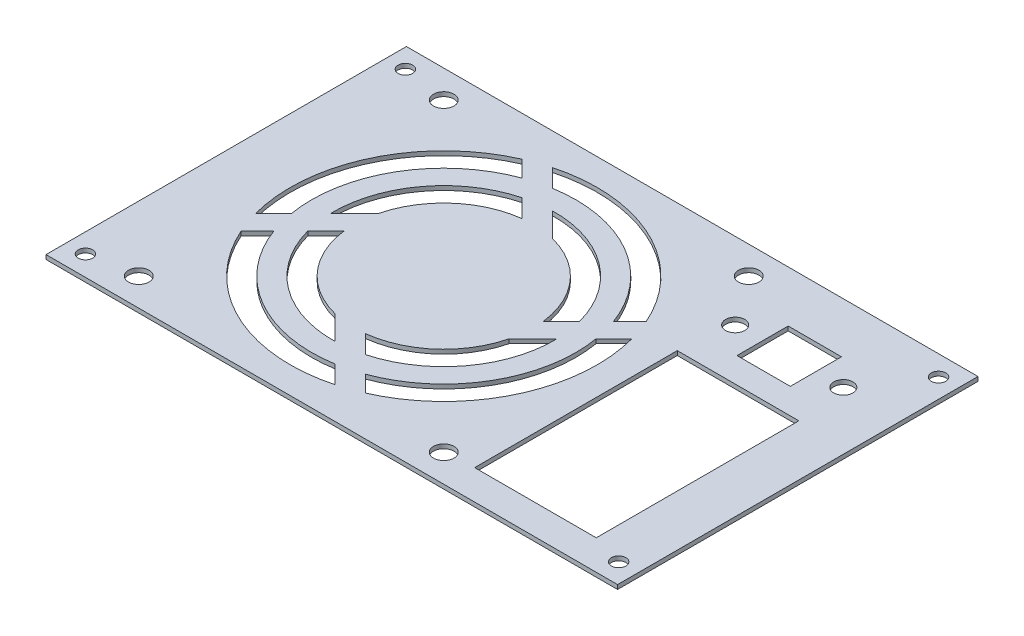
SolidWorks part; units mm, degrees
material "Thornel Mat VMA"
ref_plane "Front Plane" through (0, 0, 0) normal (0, 0, 1) x (1, 0, 0)
ref_plane "Top Plane" through (0, 0, 0) normal (0, 1, 0) x (1, 0, 0)
ref_plane "Right Plane" through (0, 0, 0) normal (1, 0, 0) x (0, 0, -1)
sketch "Sketch1" plane through (0, 0, 0) normal (0, 1, 0) x (1, 0, 0)
  line L1 (0, 0) -> (134, 0)
  line L2 (0, 0) -> (0, 84.5)
  line L3 (0, 84.5) -> (134, 84.5)
  line L4 (134, 0) -> (134, 84.5)
  dimension "D1" = 134
  dimension "D2" = 84.5
extrude "Boss-Extrude1" add sketch "Sketch1" along normal blind 1
sketch "Sketch2" plane through (0, 1, 0) normal (0, 1, 0) x (1, 0, 0)
  line L0 (67, 42.25) -> (67, 84.5) construction
  line L2 (134, 84.5) -> (0, 84.5) construction
  line L3 (129.5, 79.75) -> (4.5, 79.75) construction
  line L4 (129.5, 79.75) -> (129.5, 4.75) construction
  line L5 (129.5, 4.75) -> (4.5, 4.75) construction
  line L6 (4.5, 79.75) -> (4.5, 4.75) construction
  line L7 (129.5, 79.75) -> (4.5, 4.75) construction
  line L8 (129.5, 4.75) -> (4.5, 79.75) construction
  line L11 (0, 0) -> (134, 0) construction
  line L13 (134, 0) -> (134, 84.5) construction
  line L14 (67, 42.25) -> (134, 42.25) construction
  line L15 (67, 42.25) -> (0, 42.25) construction
  line L16 (0, 84.5) -> (0, 0) construction
  line L17 (67, 42.25) -> (67, 0) construction
  circle A0 centre (4.5, 4.75) radius 1.6
  circle A1 centre (4.5, 79.75) radius 1.6
  circle A2 centre (129.5, 79.75) radius 1.6
  circle A3 centre (129.5, 4.75) radius 1.6
  point P8 (67, 42.25)
  dimension "D1" = 3.2
  dimension "D2" = 125
  dimension "D3" = 75
hole_wizard "M3 Clearance Hole1" positions "Sketch4" profile "Sketch3" hole size "M3" standard "ANSI Metric"
sketch "Sketch4" plane through (0, 1, 0) normal (0, 1, 0) x (1, 0, 0)
  point P0 (4.5, 79.75)
  point P3 (129.5, 79.75)
  point P6 (129.5, 4.75)
  point P9 (4.5, 4.75)
sketch "Sketch3" plane through (4.5, 1, -79.75) normal (1, 0, 0) x (0, 0, 1)
  line L0 (0, 0) -> (0, 6.0215)
  line L1 (0, 6.0215) -> (1.7, 5)
  line L2 (1.7, 5) -> (1.7, 0)
  line L5 (1.7, 0) -> (0, 0)
  line L10 (0, 6.0215) -> (-1.7, 5) construction
  line L11 (0, -6.35) -> (0, 107.95) construction
  dimension "Hole Dia." = 3.4
  dimension "Hole Depth" = 5
  dimension "Drill Angle" = 118
sketch "Sketch5" plane through (0, 1, 0) normal (0, 1, 0) x (1, 0, 0)
  line L0 (0, 42.25) -> (51, 42.25) construction
  line L1 (15.25, 78) -> (86.75, 78) construction
  line L2 (15.25, 78) -> (15.25, 6.5) construction
  line L3 (15.25, 6.5) -> (86.75, 6.5) construction
  line L4 (86.75, 78) -> (86.75, 6.5) construction
  line L5 (15.25, 78) -> (86.75, 6.5) construction
  line L6 (15.25, 6.5) -> (86.75, 78) construction
  line L7 (0, 84.5) -> (0, 0) construction
  point P0 (51, 42.25)
  dimension "D1" = 71.5
  dimension "D2" = 51
hole_wizard "M4 Clearance Hole1" positions "Sketch7" profile "Sketch8" hole size "M4" standard "ANSI Metric" end condition through all
sketch "Sketch7" plane through (0, 1, 0) normal (0, 1, 0) x (1, 0, 0)
  point P0 (15.25, 78)
  point P3 (86.75, 78)
  point P6 (86.75, 6.5)
  point P9 (15.25, 6.5)
sketch "Sketch8" plane through (15.25, 1, -78) normal (1, 0, 0) x (0, 0, 1)
  line L0 (0, 0) -> (0, 1)
  line L1 (0, 1) -> (2.4, 1)
  line L2 (2.4, 1) -> (2.4, 0)
  line L5 (2.4, 0) -> (0, 0)
  line L11 (0, -6.35) -> (0, 107.95) construction
  dimension "Thru Hole Dia." = 4.8
  dimension "Thru Hole Depth" = 1
sketch "Sketch9" plane through (0, 1, 0) normal (0, 1, 0) x (1, 0, 0)
  line L0 (107.75, 30.75) -> (107.75, 66.5) construction
  line L1 (93.5, 7) -> (122, 7)
  line L2 (93.5, 7) -> (93.5, 54.5)
  line L3 (93.5, 54.5) -> (122, 54.5)
  line L4 (122, 7) -> (122, 54.5)
  line L5 (93.5, 7) -> (122, 54.5) construction
  line L6 (93.5, 54.5) -> (122, 7) construction
  line L7 (0, 0) -> (134, 0) construction
  line L8 (101.5, 72.5) -> (114, 72.5)
  line L9 (101.5, 72.5) -> (101.5, 60.5)
  line L10 (101.5, 60.5) -> (114, 60.5)
  line L11 (114, 72.5) -> (114, 60.5)
  line L12 (101.5, 72.5) -> (114, 60.5) construction
  line L13 (101.5, 60.5) -> (114, 72.5) construction
  line L14 (134, 0) -> (134, 84.5) construction
  point P0 (107.75, 30.75)
  dimension "D1" = 28.5
  dimension "D2" = 47.5
  dimension "D3" = 12
  dimension "D4" = 12.5
  dimension "D5" = 6
  dimension "D6" = 7
  dimension "D7" = 12
extrude "Cut-Extrude1" cut sketch "Sketch9" against normal through all
sketch "Sketch10" plane through (0, 1, 0) normal (0, 1, 0) x (1, 0, 0)
  line L0 (107.75, 72.5) -> (107.75, 60.5) construction
  line L1 (114, 72.5) -> (101.5, 72.5) construction
  line L2 (101.5, 60.5) -> (114, 60.5) construction
  line L3 (95.075, 66.5) -> (120.425, 66.5) construction
  point P8 (107.75, 66.5)
  dimension "D1" = 25.35
hole_wizard "M4 Clearance Hole2" positions "Sketch12" profile "Sketch11" hole size "M4" standard "ANSI Metric" end condition through all
sketch "Sketch12" plane through (0, 1, 0) normal (0, 1, 0) x (1, 0, 0)
  point P0 (95.075, 66.5)
  point P3 (120.425, 66.5)
sketch "Sketch11" plane through (95.075, 1, -66.5) normal (1, 0, 0) x (0, 0, 1)
  line L0 (0, 0) -> (0, 1)
  line L1 (0, 1) -> (2.25, 1)
  line L2 (2.25, 1) -> (2.25, 0)
  line L5 (2.25, 0) -> (0, 0)
  line L11 (0, -6.35) -> (0, 107.95) construction
  dimension "Thru Hole Dia." = 4.5
  dimension "Thru Hole Depth" = 1
sketch "Sketch14" plane through (0, 1, 0) normal (0, 1, 0) x (1, 0, 0)
  line L0 (15.25, 78) -> (86.75, 6.5) construction
  line L1 (63.0208, 30.2292) -> (87.8402, 55.0485) construction
  line L2 (39.0036, 30.2536) -> (63.8229, 5.4343) construction
  line L3 (39.028, 54.2708) -> (14.2087, 29.4515) construction
  line L4 (63.0452, 54.2464) -> (38.2259, 79.0657) construction
  line L5 (71.8543, 44.7195) -> (76.1141, 48.9793)
  line L6 (41.6825, 77.0233) -> (45.8814, 72.8245)
  line L7 (50.4614, 68.2444) -> (56.0794, 62.6265)
  line L8 (80.0921, 52.9574) -> (83.9305, 56.7958)
  line L9 (53.4695, 21.3957) -> (57.7293, 17.1359)
  line L10 (76.9944, 42.7886) -> (71.3765, 37.1706)
  line L11 (85.7733, 51.5675) -> (81.5745, 47.3686)
  line L12 (61.7074, 13.1579) -> (65.5458, 9.3195)
  line L13 (30.1457, 39.7805) -> (25.8859, 35.5207)
  line L14 (51.5386, 16.2556) -> (45.9206, 21.8735)
  line L15 (60.3175, 7.4767) -> (56.1186, 11.6755)
  line L16 (21.9079, 31.5426) -> (18.0695, 27.7042)
  line L17 (48.5305, 63.1043) -> (44.2707, 67.3641)
  line L18 (25.0056, 41.7114) -> (30.6235, 47.3294)
  line L19 (16.2267, 32.9325) -> (20.4255, 37.1314)
  line L20 (40.2926, 71.3421) -> (36.4542, 75.1805)
  circle A0 centre (51, 42.25) radius 39 construction
  circle A1 centre (51, 42.25) radius 17 construction
  arc A2 (83.9305, 56.7958) -> (41.6825, 77.0233) centre (51, 42.25) ccw
  arc A3 (80.0921, 52.9574) -> (45.8814, 72.8245) centre (51, 42.25) ccw
  arc A4 (76.1141, 48.9793) -> (50.4614, 68.2444) centre (51, 42.25) ccw
  arc A5 (71.8543, 44.7195) -> (56.0794, 62.6265) centre (51, 42.25) ccw
  arc A6 (53.4695, 21.3957) -> (71.3765, 37.1706) centre (51, 42.25) ccw
  arc A7 (57.7293, 17.1359) -> (76.9944, 42.7886) centre (51, 42.25) ccw
  arc A8 (61.7074, 13.1579) -> (81.5745, 47.3686) centre (51, 42.25) ccw
  arc A9 (65.5458, 9.3195) -> (85.7733, 51.5675) centre (51, 42.25) ccw
  arc A10 (30.1457, 39.7805) -> (45.9206, 21.8735) centre (51, 42.25) ccw
  arc A11 (25.8859, 35.5207) -> (51.5386, 16.2556) centre (51, 42.25) ccw
  arc A12 (21.9079, 31.5426) -> (56.1186, 11.6755) centre (51, 42.25) ccw
  arc A13 (18.0695, 27.7042) -> (60.3175, 7.4767) centre (51, 42.25) ccw
  arc A14 (48.5305, 63.1043) -> (30.6235, 47.3294) centre (51, 42.25) ccw
  arc A15 (44.2707, 67.3641) -> (25.0056, 41.7114) centre (51, 42.25) ccw
  arc A16 (40.2926, 71.3421) -> (20.4255, 37.1314) centre (51, 42.25) ccw
  arc A17 (36.4542, 75.1805) -> (16.2267, 32.9325) centre (51, 42.25) ccw
  point P18 (51.0244, 42.25)
  point P51 (51, 42.25)
  dimension "D1" = 34
  dimension "D2" = 78
  dimension "D6" = 5
  dimension "D7" = 5
  dimension "D8" = 5
  dimension "D9" = 4
  dimension "D4" = 1
  dimension "D5" = 4
  dimension "D3" = 4
  dimension "D10" = 4
extrude "Cut-Extrude5" cut sketch "Sketch14" against normal through all
